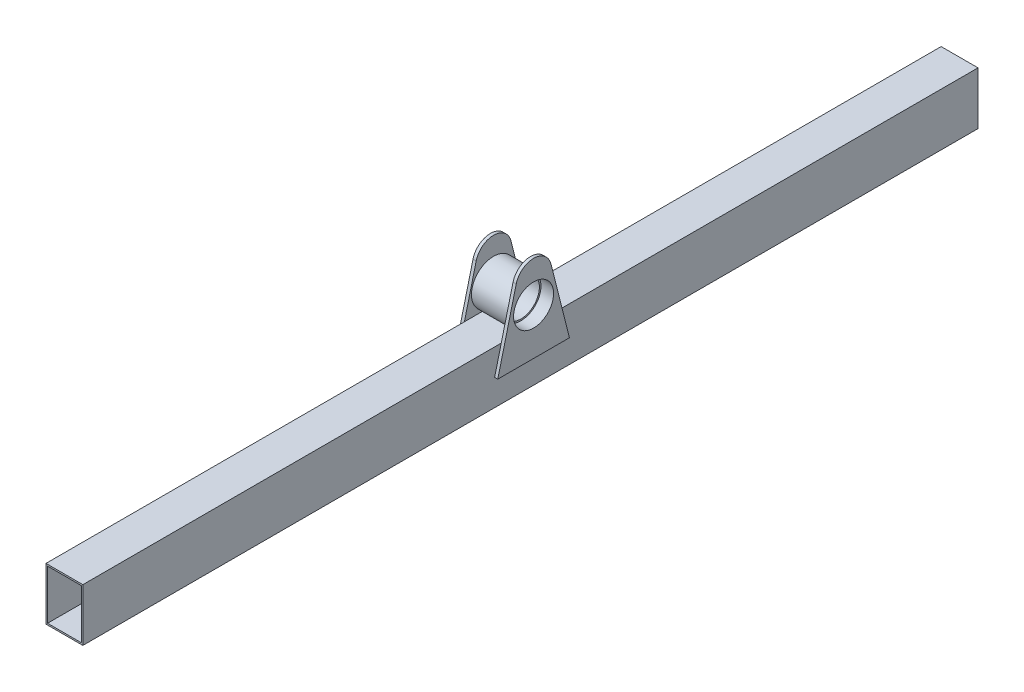
SolidWorks part; units mm, degrees
ref_plane "Front Plane" through (0, 0, 0) normal (0, 0, 1) x (1, 0, 0)
ref_plane "Top Plane" through (0, 0, 0) normal (0, 1, 0) x (1, 0, 0)
ref_plane "Right Plane" through (0, 0, 0) normal (1, 0, 0) x (0, 0, -1)
sketch "Sketch1" plane through (0, 0, 0) normal (0, 0, 1) x (1, 0, 0)
  line L1 (-16, 23.5) -> (16, 23.5)
  line L2 (-16, 23.5) -> (-16, -23.5)
  line L3 (-16, -23.5) -> (16, -23.5)
  line L4 (16, 23.5) -> (16, -23.5)
  line L5 (-16, 23.5) -> (16, -23.5) construction
  line L6 (-16, -23.5) -> (16, 23.5) construction
  line L7 (-17.5, 25) -> (17.5, 25)
  line L8 (-17.5, 25) -> (-17.5, -25)
  line L9 (-17.5, -25) -> (17.5, -25)
  line L10 (17.5, 25) -> (17.5, -25)
  line L11 (-17.5, 25) -> (17.5, -25) construction
  line L12 (-17.5, -25) -> (17.5, 25) construction
  point P0 (0, 0)
  point P7 (0, 0)
  dimension "D1" = 47
  dimension "D2" = 32
  dimension "D3" = 50
  dimension "D4" = 35
extrude "Boss-Extrude1" add sketch "Sketch1" along normal blind 460
sketch "Sketch2" plane through (-17.5, 0, 0) normal (-1, 0, 0) x (0, 0, 1)
  line L2 (35, 0) -> (35, 72.054) construction
  line L3 (1, 0) -> (7.2961, 25)
  line L4 (460, 25) -> (0, 25) construction
  line L5 (69, 0) -> (62.7039, 25)
  line L6 (7.2961, 25) -> (18.5, 69.4873)
  line L7 (62.7039, 25) -> (51.5, 69.4873)
  line L8 (1, 0) -> (69, 0)
  arc A0 (18.5, 69.4873) -> (51.5, 69.4873) centre (35, 65.3319) cw
  dimension "D1" = 34
  dimension "D2" = 33
extrude "Boss-Extrude2" add sketch "Sketch2" along normal blind 3
sketch "Sketch3" plane through (-20.5, 0, 0) normal (-1, 0, 0) x (0, 0, 1)
  line L0 (35, 82.3471) -> (35, 0) construction
  line L1 (1, 0) -> (69, 0) construction
  line L2 (7.2961, 25) -> (62.7039, 25) construction
  arc A0 (51.5, 69.4873) -> (18.5, 69.4873) centre (35, 65.3319) ccw construction
  circle A1 centre (35, 44) radius 19
  dimension "D1" = 38
extrude "Cut-Extrude1" cut sketch "Sketch3" against normal blind 3
mirror "Mirror1" about plane through (0, 0, 0) normal (1, 0, 0) of "Cut-Extrude1", "Boss-Extrude2"
sketch "Sketch4" plane through (-20.5, 0, 0) normal (-1, 0, 0) x (0, 0, 1)
  circle A0 centre (35, 44) radius 19
  circle A1 centre (35, 44) radius 21
  dimension "D1" = 38
  dimension "D2" = 42
sketch "Sketch5" plane through (-17.5, 0, 0) normal (1, 0, 0) x (0, 0, -1)
  circle A0 centre (-35, 44) radius 21
  circle A1 centre (-35, 44) radius 17.5
  dimension "D1" = 42
  dimension "D2" = 35
extrude "Boss-Extrude7" add sketch "Sketch5" along normal up to surface (35 mm away) up to face at (17.5, 41.9724, 35)
sketch "Sketch6" plane through (17.5, 0, 0) normal (1, 0, 0) x (0, 0, -1)
  circle A0 centre (-35, 44) radius 19
extrude "Cut-Extrude2" cut sketch "Sketch6" against normal blind 9
mirror "Mirror2" about plane through (0, 0, 0) normal (1, 0, 0) of "Cut-Extrude2"
extrude "Boss-Extrude8" add sketch "Sketch1<2>" against normal blind 390
sketch "Sketch1<2>" plane through (0, 0, 0) normal (0, 0, 1) x (1, 0, 0) same geometry as "Sketch1"
sketch "Sketch7" plane through (-17.5, 0, 0) normal (-1, 0, 0) x (0, 0, 1)
  line L1 (1, 0) -> (69, 0) construction
  circle A0 centre (420, 0) radius 10
  circle A1 centre (-350, 0) radius 10
  point P7 (35, 0)
  dimension "D2" = 20
  dimension "D3" = 20
  dimension "D1" = 420
  dimension "D4" = 385
